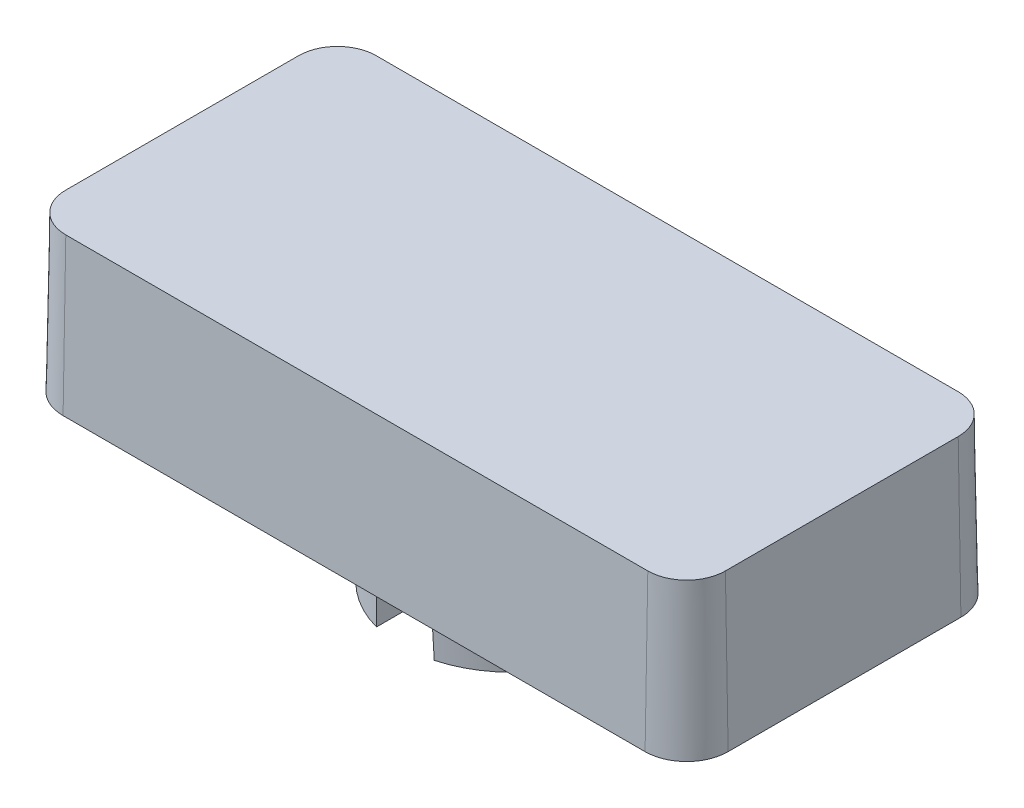
SolidWorks part; units mm, degrees
ref_plane "Front Plane" through (0, 0, 0) normal (0, 0, 1) x (1, 0, 0)
ref_plane "Top Plane" through (0, 0, 0) normal (0, 1, 0) x (1, 0, 0)
ref_plane "Right Plane" through (0, 0, 0) normal (1, 0, 0) x (0, 0, -1)
sketch "Sketch1" plane through (0, 0, 0) normal (0, 1, 0) x (1, 0, 0)
  line L1 (-7.5, -4) -> (7.5, -4)
  line L2 (-8.5, -3) -> (-8.5, 3)
  line L3 (-7.5, 4) -> (7.5, 4)
  line L4 (8.5, -3) -> (8.5, 3)
  line L5 (-8.5, -4) -> (8.5, 4) construction
  line L6 (-8.5, 4) -> (8.5, -4) construction
  arc A0 (-8.5, 3) -> (-7.5, 4) centre (-7.5, 3) cw
  arc A1 (8.5, 3) -> (7.5, 4) centre (7.5, 3) ccw
  arc A2 (8.5, -3) -> (7.5, -4) centre (7.5, -3) cw
  arc A3 (-7.5, -4) -> (-8.5, -3) centre (-7.5, -3) cw
  point P0 (0, 0)
  dimension "D3" = 1
  dimension "D1" = 17
  dimension "D2" = 8
extrude "Boss-Extrude1" add sketch "Sketch1" against normal blind 4 draft 1 draft outward yes
shell "Shell1" thickness 0.5 removed face at (0, -4, 0)
sketch "Sketch2" plane through (0, -0.5, 0) normal (0, -1, 0) x (1, 0, 0)
  line L0 (-0.6, 2.9308) -> (-0.6, 0.6)
  line L1 (-2.9308, 0.6) -> (-0.6, 0.6)
  line L2 (0, -55) -> (0, 55) construction
  line L3 (2.2, 0) -> (-2.2, 0) construction
  line L4 (-2.9308, -0.6) -> (-0.6, -0.6)
  line L5 (0.6, 2.9308) -> (0.6, 0.6)
  line L6 (-0.6, -0.6) -> (-0.6, -2.9308)
  line L7 (0.6, -0.6) -> (0.6, -2.9308)
  line L8 (0.6, -0.6) -> (2.9308, -0.6)
  line L9 (0.6, 0.6) -> (2.9308, 0.6)
  arc A0 (-2.9308, -0.6) -> (-0.6, -2.9308) centre (0, 0) ccw
  arc A1 (2.9308, 0.6) -> (0.6, 2.9308) centre (0, 0) ccw
  arc A2 (-0.6, 2.9308) -> (-2.9308, 0.6) centre (0, 0) ccw
  arc A3 (0.6, -2.9308) -> (2.9308, -0.6) centre (0, 0) ccw
  dimension "D1" = 0.6
  dimension "D2" = 0.6
extrude "Boss-Extrude2" add sketch "Sketch2" along normal blind 5.5 draft 1.5
